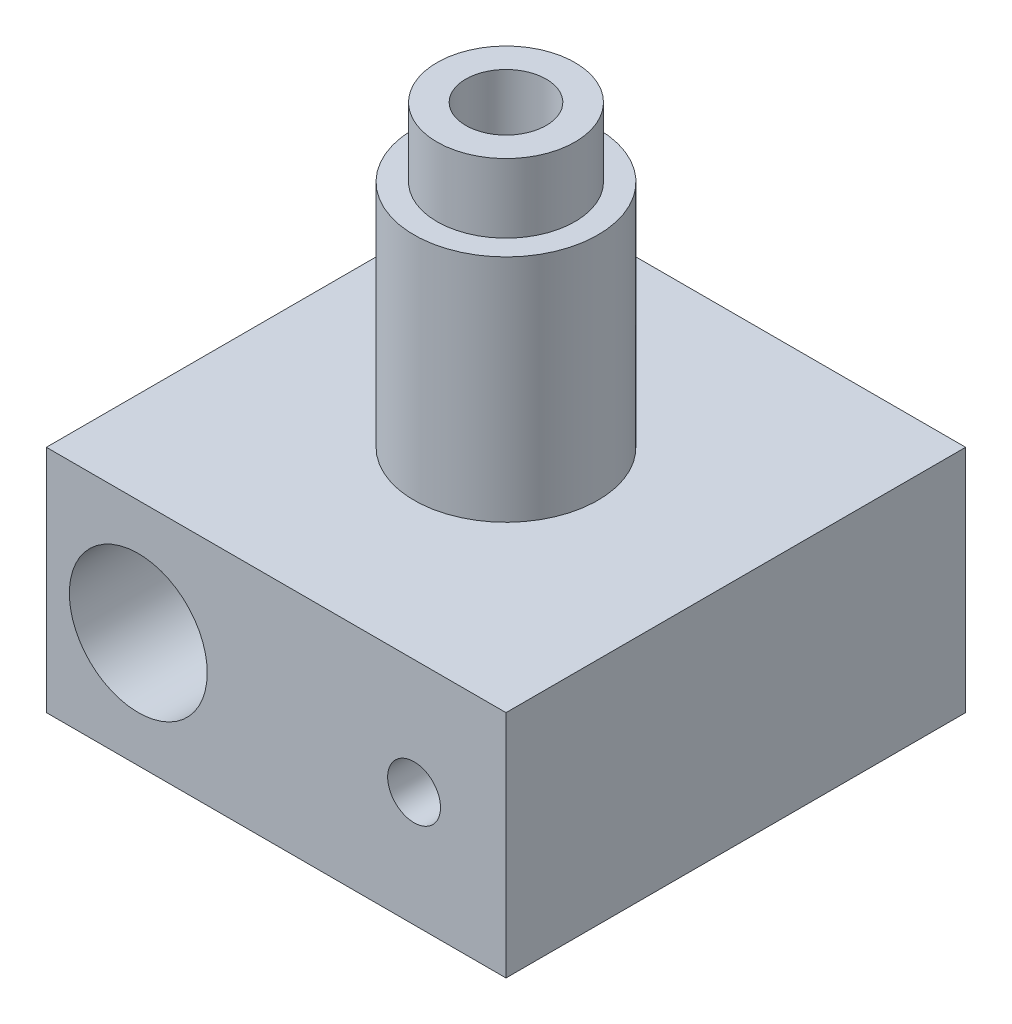
SolidWorks part; units mm, degrees
material "7075-T6 (SN)"
ref_plane "Piano frontale" through (0, 0, 0) normal (0, 0, 1) x (1, 0, 0)
ref_plane "Piano superiore" through (0, 0, 0) normal (0, 1, 0) x (1, 0, 0)
ref_plane "Piano destro" through (0, 0, 0) normal (1, 0, 0) x (0, 0, -1)
sketch "Schizzo1" plane through (0, 0, 0) normal (0, 0, 1) x (1, 0, 0)
  line L0 (-0.15, 0) -> (-0.15, -4)
  line L1 (-0.15, -4) -> (-0.5, -4)
  line L2 (-0.5, -4) -> (-3, -2)
  line L3 (-3, -2) -> (-3, 0)
  line L4 (-3, 0) -> (-0.15, 0)
  line L5 (0, -26.5282) -> (0, 14.9614) construction
  dimension "D1" = 0.3
  dimension "D2" = 4
  dimension "D3" = 6
  dimension "D4" = 1
  dimension "D5" = 2
revolve "Rivoluzione1" add sketch "Schizzo1" angle 360 about L5
sketch "Schizzo2" plane through (0, 0, 0) normal (0, 1, 0) x (1, 0, 0)
  line L0 (0, 0) -> (0, -10.5487) construction
  line L6 (10, -10) -> (-10, -10)
  line L7 (10, -10) -> (10, 10)
  line L8 (10, 10) -> (-10, 10)
  line L9 (-10, -10) -> (-10, 10)
  line L10 (10, -10) -> (-10, 10) construction
  line L11 (10, 10) -> (-10, -10) construction
  circle A1 centre (0, 0) radius 0.15 construction
  circle A2 centre (0, 0) radius 0.15
  dimension "D1" = 20
  dimension "D2" = 20
extrude "Estrusione-Estrusione1" add sketch "Schizzo2" along normal blind 10
sketch "Schizzo3" plane through (0, 10, 0) normal (0, 1, 0) x (1, 0, 0)
  circle A0 centre (0, 0) radius 4
extrude "Estrusione-Sottile1" add sketch "Schizzo3" along normal blind 13 thin thin type one direction reverse wall 2.25
sketch "Schizzo4" plane through (0, 0, 10) normal (0, 0, 1) x (1, 0, 0)
  line L0 (-10, 5) -> (10, 5) construction
  line L1 (-10, 10) -> (-10, 0) construction
  line L2 (10, 10) -> (10, 0) construction
  circle A0 centre (-6, 5) radius 3
  circle A1 centre (6, 5) radius 1.15
  dimension "D1" = 4
  dimension "D2" = 6
  dimension "D3" = 2.3
  dimension "D4" = 4
extrude "Taglio-Estrusione1" cut sketch "Schizzo4" against normal up to next
sketch "Schizzo5" plane through (0, 0, -10) normal (0, 0, -1) x (-1, 0, 0)
  circle A0 centre (-6, 5) radius 3
hole_wizard "Foro filettato M6x1.0-1" positions "Schizzo7" profile "Schizzo6" tap size "M6x1.0" standard "Ansi Metric"
sketch "Schizzo7" plane through (0, 0, -10) normal (0, 0, -1) x (-1, 0, 0)
  point P1 (-6, 5)
sketch "Schizzo6" plane through (6, 5, -10) normal (1, 0, 0) x (0, 1, 0)
  line L0 (0, 0) -> (0, 13.5022)
  line L1 (0, 13.5022) -> (2.5, 12)
  line L2 (2.5, 12) -> (2.5, 0.525)
  line L3 (2.5, 0.525) -> (3.025, 0)
  line L5 (3.025, 0) -> (0, 0)
  line L6 (-2.5, 0.525) -> (-3.025, 0) construction
  line L10 (0, 13.5022) -> (-2.5, 12) construction
  line L11 (0, -6.35) -> (0, 107.95) construction
  dimension "Tap Drill Dia." = 5
  dimension "Tap Drill Depth" = 12
  dimension "Near C'Sink Dia." = 6.05
  dimension "Near C'Sink Angle" = 90
  dimension "Drill Angle" = 118
cosmetic thread "Filettatura del foro1" parameters "D1"=12, "D2"=6
sketch "Schizzo8" plane through (0, 23, 0) normal (0, 1, 0) x (1, 0, 0)
  circle A0 centre (0, 0) radius 3
extrude "Taglio-Estrusione-Sottile1" cut sketch "Schizzo8" against normal blind 3 thin thin type one direction wall 10
equation "\"50di\"=45"
